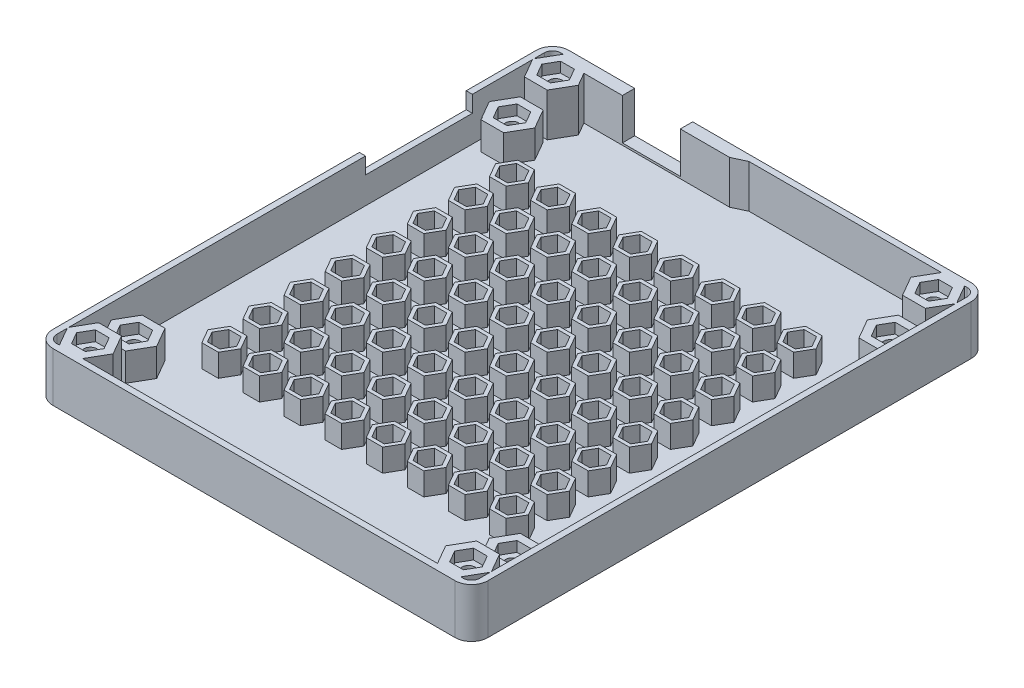
SolidWorks part; units mm, degrees
ref_plane "Přední rovina" through (0, 0, 0) normal (0, 0, 1) x (1, 0, 0)
ref_plane "Horní rovina" through (0, 0, 0) normal (0, 1, 0) x (1, 0, 0)
ref_plane "Pravá rovina" through (0, 0, 0) normal (1, 0, 0) x (0, 0, -1)
sketch "Skica1" plane through (0, 0, 0) normal (0, 1, 0) x (1, 0, 0)
  line L0 (0, 0) -> (-100, 100) construction
  line L1 (-50, 50) -> (50, 50) construction
  line L2 (-50, 50) -> (-50, -50) construction
  line L3 (-50, -50) -> (50, -50) construction
  line L4 (50, 50) -> (50, -50) construction
  line L5 (-50, 50) -> (50, -50) construction
  line L6 (-50, -50) -> (50, 50) construction
  line L7 (-47.6743, 43.1) -> (-44.3257, 43.1)
  line L8 (-44.3257, 43.1) -> (-42.6514, 46)
  line L9 (-42.6514, 46) -> (-44.3257, 48.9)
  line L10 (-44.3257, 48.9) -> (-47.6743, 48.9)
  line L11 (-47.6743, 48.9) -> (-49.3486, 46)
  line L12 (-49.3486, 46) -> (-47.6743, 43.1)
  line L13 (-48.7713, 41.2) -> (-43.2287, 41.2)
  line L14 (-43.2287, 41.2) -> (-40.4574, 46)
  line L15 (-40.4574, 46) -> (-43.2287, 50.8)
  line L16 (-43.2287, 50.8) -> (-48.7713, 50.8)
  line L17 (-48.7713, 50.8) -> (-51.5426, 46)
  line L18 (-51.5426, 46) -> (-48.7713, 41.2)
  line L19 (0, 81.3987) -> (0, -91.9033) construction
  line L20 (-42.6514, 56.6) -> (-44.3257, 59.5)
  line L21 (-44.3257, 59.5) -> (-47.6743, 59.5)
  line L22 (-47.6743, 59.5) -> (-49.3486, 56.6)
  line L23 (-49.3486, 56.6) -> (-47.6743, 53.7)
  line L24 (-47.6743, 53.7) -> (-44.3257, 53.7)
  line L25 (-44.3257, 53.7) -> (-42.6514, 56.6)
  line L26 (-48.7713, 51.8) -> (-43.2287, 51.8)
  line L27 (-43.2287, 51.8) -> (-40.4574, 56.6)
  line L28 (-40.4574, 56.6) -> (-43.2287, 61.4)
  line L29 (-43.2287, 61.4) -> (-48.7713, 61.4)
  line L30 (-48.7713, 61.4) -> (-51.5426, 56.6)
  line L31 (-51.5426, 56.6) -> (-48.7713, 51.8)
  line L36 (74.9355, -74.9355) -> (-74.9355, 74.9355) construction
  line L37 (74.9355, 74.9355) -> (-74.9355, -74.9355) construction
  line L38 (-52.9426, -62.8) -> (52.9426, -62.8)
  line L39 (-52.9426, -62.8) -> (-52.9426, 62.8)
  line L40 (-52.9426, 62.8) -> (52.9426, 62.8)
  line L41 (52.9426, -62.8) -> (52.9426, 62.8)
  line L42 (-52.9426, -62.8) -> (52.9426, 62.8) construction
  line L43 (-52.9426, 62.8) -> (52.9426, -62.8) construction
  line L44 (-106.951, 0) -> (125.2961, 0) construction
  line L45 (-46, 37.8836) -> (-46, 68.4593) construction
  line L47 (-51.4426, -61.3) -> (51.4426, -61.3)
  line L48 (-51.4426, -61.3) -> (-51.4426, 61.3)
  line L49 (-51.4426, 61.3) -> (51.4426, 61.3)
  line L50 (51.4426, -61.3) -> (51.4426, 61.3)
  line L51 (-51.4426, -61.3) -> (51.4426, 61.3) construction
  line L52 (-51.4426, 61.3) -> (51.4426, -61.3) construction
  circle A0 centre (-46, 46) radius 2.9 construction
  circle A1 centre (-46, 46) radius 4.8 construction
  circle A2 centre (-46, 56.6) radius 2.9 construction
  circle A3 centre (-46, 56.6) radius 4.8 construction
  circle A4 centre (-46, 46) radius 1.6
  circle A5 centre (-46, 56.6) radius 1.6
  point P0 (0, 0)
  point P7 (-41.8431, 43.6)
  dimension "D9" = 1.5
  dimension "D10" = 1.5
  dimension "D11" = 0.1
  dimension "D12" = 0.1
  dimension "D13" = 3.2
  dimension "D14" = 3.2
  dimension "D1" = 100
  dimension "D2" = 100
  dimension "D3" = 5.8
  dimension "D4" = 4
  dimension "D5" = 9.6
  dimension "D6" = 5.8
  dimension "D7" = 9.6
  dimension "D8" = 1
extrude "Přidat vysunutím25" add sketch "Skica1" against normal blind 3 contours L49 L48 L30 | L20 L21 L22 L23 L24 L25 | L7 L8 L9 L10 L11 L12 | L48 L47 L50 L49 | L13 L14 L15 L16 L17 L18 | L26 L27 L28 L29 L30 L31 region at (-50.5714, 0, -59.7911)
extrude "Přidat vysunutím26" add sketch "Skica1<21>" against normal blind 3 and the other way blind 10.5 contours L38 L41 L40 L39 L50 L47 L48 L18 L17 L31 L30 L49 L29 L28 | L18 L48 L17 | L31 L48 L30 | L30 L49 L28 L29 region at (-51.4759, 0, -46) region at (-51.4759, 0, -56.6) region at (-46, 0, -61.3498) region at (-52.7783, 0, 0)
sketch "Skica1<21>" plane through (0, 0, 0) normal (0, 1, 0) x (1, 0, 0) same geometry as "Skica1"
extrude "Přidat vysunutím28" add sketch "Skica1<23>" along normal blind 6.8 contours L48 L18 L13 L14 L15 L16 L17 L12 L11 L10 L9 L8 L7 | L18 L48 L17 region at (-49.9806, 0, -43.5863) region at (-51.4759, 0, -46)
sketch "Skica1<23>" plane through (0, 0, 0) normal (0, 1, 0) x (1, 0, 0) same geometry as "Skica1"
extrude "Přidat vysunutím29" add sketch "Skica1<24>" along normal blind 4.3 contours L11 L12 L7 L8 L9 L10 region at (-48.4347, 0, -44.5943)
sketch "Skica1<24>" plane through (0, 0, 0) normal (0, 1, 0) x (1, 0, 0) same geometry as "Skica1"
pattern_linear "LinPole3" count 2 spacing 92 along (1, 0, 0) count 2 spacing 92 along (0, 0, 1) of "Přidat vysunutím28", "Přidat vysunutím29"
extrude "Přidat vysunutím30" add sketch "Skica1<25>" along normal blind 10.5 contours L49 L30 L48 L31 L26 L27 L28 L25 L24 L23 L22 L21 L20 | L30 L49 L28 L29 | L31 L48 L30 region at (-51.2973, 0, -56.6) region at (-51.4759, 0, -56.6) region at (-46, 0, -61.3498)
sketch "Skica1<25>" plane through (0, 0, 0) normal (0, 1, 0) x (1, 0, 0) same geometry as "Skica1"
extrude "Přidat vysunutím31" add sketch "Skica1<26>" along normal blind 8 contours L24 L25 L20 L21 L22 L23 A5 region at (-43.5653, 0, -55.1943)
sketch "Skica1<26>" plane through (0, 0, 0) normal (0, 1, 0) x (1, 0, 0) same geometry as "Skica1"
pattern_linear "LinPole4" count 2 spacing 92 along (1, 0, 0) count 2 spacing 113.2 along (0, 0, 1) of "Přidat vysunutím31", "Přidat vysunutím30"
fillet "Zaoblit4" radius 4 4 edges at (-52.9426, 3.75, 62.8) (52.9426, 3.75, 62.8) (52.9426, 3.75, -62.8) (-52.9426, 3.75, -62.8)
sketch "Skica9" plane through (-52.9426, 0, 0) normal (-1, 0, 0) x (0, 0, 1)
  line L0 (58.8, 10.5) -> (-58.8, 10.5) construction
  line L1 (-15.8, 6.5) -> (-41.8, 6.5)
  line L2 (-15.8, 6.5) -> (-15.8, 10.5)
  line L3 (-15.8, 10.5) -> (-41.8, 10.5)
  line L4 (-41.8, 6.5) -> (-41.8, 10.5)
  line L5 (-15.8, 6.5) -> (-41.8, 10.5) construction
  line L6 (-15.8, 10.5) -> (-41.8, 6.5) construction
  line L7 (-62.8, -3) -> (-62.8, 10.5) construction
  point P0 (-28.8, 8.5)
  dimension "D1" = 26
  dimension "D2" = 21
  dimension "D3" = 4
extrude "Odebrat vysunutím1" cut sketch "Skica9" against normal blind 4 contours L4 L3 L2 L1
sketch "Skica10" plane through (0, 0, -62.8) normal (0, 0, -1) x (-1, 0, 0)
  line L0 (48.9426, 10.5) -> (-48.9426, 10.5) construction
  line L1 (18.8426, 0.5) -> (32.9426, 0.5)
  line L2 (18.8426, 0.5) -> (18.8426, 10.5)
  line L3 (18.8426, 10.5) -> (32.9426, 10.5)
  line L4 (32.9426, 0.5) -> (32.9426, 10.5)
  line L5 (52.9426, 10.5) -> (52.9426, -3) construction
  dimension "D1" = 10
  dimension "D2" = 14.1
  dimension "D3" = 20
extrude "Odebrat vysunutím2" cut sketch "Skica10" against normal blind 5
sketch "Skica11" plane through (0, 0, 0) normal (0, 1, 0) x (1, 0, 0)
  line L0 (-43.171, 61.3) -> (43.171, 61.3) construction
  line L1 (-35, -35) -> (35, -35) construction
  line L2 (-35, -35) -> (-35, 35) construction
  line L3 (-35, 35) -> (35, 35) construction
  line L4 (35, -35) -> (35, 35) construction
  line L5 (-35, -35) -> (35, 35) construction
  line L6 (-35, 35) -> (35, -35) construction
  line L7 (-33.5, 32.4019) -> (-32, 35)
  line L8 (-32, 35) -> (-33.5, 37.5981)
  line L9 (-33.5, 37.5981) -> (-36.5, 37.5981)
  line L10 (-36.5, 37.5981) -> (-38, 35)
  line L11 (-38, 35) -> (-36.5, 32.4019)
  line L12 (-36.5, 32.4019) -> (-33.5, 32.4019)
  line L13 (-33, 31.5359) -> (-31, 35)
  line L14 (-31, 35) -> (-33, 38.4641)
  line L15 (-33, 38.4641) -> (-37, 38.4641)
  line L16 (-37, 38.4641) -> (-39, 35)
  line L17 (-39, 35) -> (-37, 31.5359)
  line L18 (-37, 31.5359) -> (-33, 31.5359)
  circle A0 centre (-35, 35) radius 2.5981 construction
  circle A1 centre (-35, 35) radius 3.4641 construction
  point P0 (0, 0)
  dimension "D1" = 70
  dimension "D2" = 3
  dimension "D3" = 4
extrude "Přidat vysunutím32" add sketch "Skica11" along normal blind 5.5
pattern_linear "LinPole5" count 8 spacing 10 along (1, 0, 0) count 8 spacing 10 along (0, 0, 1) of "Přidat vysunutím32"
sketch "Skica12" plane through (52.9426, 0, 0) normal (1, 0, 0) x (0, 0, -1)
  line L0 (-58.8, -3) -> (58.8, -3) construction
  line L1 (-68.1521, -1.5) -> (66.6031, -1.5)
  line L2 (-68.1521, -1.5) -> (-68.1521, -12.5491)
  line L3 (-68.1521, -12.5491) -> (66.6031, -12.5491)
  line L4 (66.6031, -1.5) -> (66.6031, -12.5491)
  dimension "D1" = 1.5
extrude "Odebrat vysunutím3" cut sketch "Skica12" against normal through all
fillet "Zaoblit5" radius 2 4 edges at (-51.4426, 5.25, 61.3) (51.4426, 5.25, 61.3) (51.4426, 5.25, -61.3) (-51.4426, 5.25, -61.3)
sketch "Skica13" plane through (0, 0, -61.3) normal (0, 0, 1) x (1, 0, 0)
  line L0 (-32.9426, 10.5) -> (-43.9426, 10.5)
  line L1 (-43.171, 10.5) -> (-32.9426, 10.5) construction
  line L2 (-43.9426, 10.5) -> (-43.9426, 0)
  line L3 (-43.171, 0) -> (43.171, 0) construction
  line L4 (-43.9426, 0) -> (-6.8426, 0)
  line L5 (-6.8426, 0) -> (-6.8426, 10.5)
  line L6 (-18.8426, 10.5) -> (43.171, 10.5) construction
  line L7 (-6.8426, 10.5) -> (-18.8426, 10.5)
  line L8 (-18.8426, 10.5) -> (-18.8426, 0.5)
  line L9 (-18.8426, 0.5) -> (-32.9426, 0.5)
  line L10 (-32.9426, 0.5) -> (-32.9426, 10.5)
  dimension "D1" = 11
  dimension "D2" = 12
extrude "Přidat vysunutím33" add sketch "Skica13" along normal blind 1.5
sketch "Skica14" plane through (0, 10.5, 0) normal (0, 1, 0) x (1, 0, 0)
  line L5 (-6.8426, 59.8) -> (-6.8426, 61.3)
  line L6 (-6.8426, 61.3) -> (43.171, 61.3) construction
  line L7 (-6.8426, 59.8) -> (-6.8426, 61.3) construction
  line L8 (-6.8426, 61.3) -> (-3.6258, 61.3)
  line L9 (-3.6258, 61.3) -> (-6.8426, 59.8)
  dimension "D1" = 25
extrude "Přidat vysunutím34" add sketch "Skica14" against normal up to next contours L9 L5 L8
